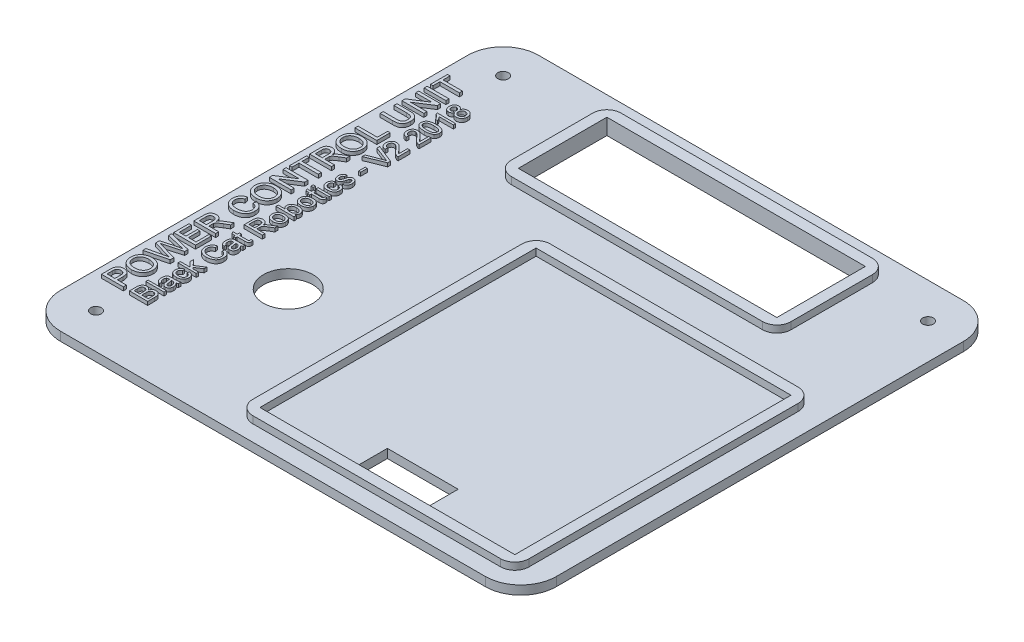
SolidWorks part; units mm, degrees
note: The reader was unsure of these and kept them because the rebuilt part matched: shared geometry of "Sketch1<3>".
ref_plane "Front Plane" through (0, 0, 0) normal (0, 0, 1) x (1, 0, 0)
ref_plane "Top Plane" through (0, 0, 0) normal (0, 1, 0) x (1, 0, 0)
ref_plane "Right Plane" through (0, 0, 0) normal (1, 0, 0) x (0, 0, -1)
sketch "Sketch1" plane through (0, 0, 0) normal (0, 1, 0) x (1, 0, 0)
  line L0 (0, 0) -> (0, -40) construction
  line L1 (0, 0) -> (101.6, 0)
  line L2 (0, 0) -> (0, 48.26)
  line L3 (0, 48.26) -> (101.6, 48.26)
  line L4 (101.6, 0) -> (101.6, 48.26)
  line L5 (0, 48.26) -> (101.6, 48.26)
  line L6 (0, 48.26) -> (0, 81.28)
  line L7 (0, 81.28) -> (101.6, 81.28)
  line L8 (101.6, 48.26) -> (101.6, 81.28)
  line L9 (0, -40) -> (-35, -40) construction
  line L10 (101.6, 81.28) -> (151.6, 81.28) construction
  line L11 (151.5601, 121.6473) -> (151.6, 121.28) construction
  line L12 (151.6, 121.28) -> (151.6, 81.28) construction
  line L18 (-35, -40) -> (151.6, -40)
  line L19 (-35, -40) -> (-35, 121.28)
  line L20 (-35, 121.28) -> (151.6, 121.28)
  line L21 (151.6, -40) -> (151.6, 121.28)
  circle A0 centre (0, 81.28) radius 5
  circle A1 centre (0, 48.26) radius 5
  circle A2 centre (0, 0) radius 5
  circle A3 centre (101.6, 0) radius 5
  circle A4 centre (101.6, 48.26) radius 5
  circle A5 centre (101.6, 81.28) radius 5
  dimension "D5" = 101.6
  dimension "D1" = 40
  dimension "D2" = 35
  dimension "D3" = 50
  dimension "D4" = 40
  dimension "D6" = 48.26
  dimension "D7" = 33.02
extrude "Boss-Extrude1" add sketch "Sketch1" along normal blind 5
extrude "Boss-Extrude2" add sketch "Sketch1<3>" along normal blind 25 contours L7 A0 L6 | A1 | A5 | A4 | A3 | A2
sketch "Sketch1<3>" plane through (0, 0, 0) normal (0, 1, 0) x (1, 0, 0) same geometry as "Sketch1"
fillet "Fillet1" radius 5 6 edges at (101.6, 5, -76.28) (101.6, 5, -43.26) (101.6, 5, 5) (0, 5, 5) (0, 5, -43.26) (0, 5, -76.28)
fillet "Fillet2" radius 20 4 edges at (-35, 2.5, -121.28) (151.6, 2.5, -121.28) (151.6, 2.5, 40) (-35, 2.5, 40)
sketch "Sketch5" plane through (0, 0, 0) normal (0, -1, 0) x (-1, 0, 0)
  line L2 (35, -20) -> (35, 101.28)
  line L4 (-151.6, -20) -> (-151.6, 101.28)
  line L5 (15, -40) -> (-131.6, -40)
  line L7 (15, 121.28) -> (-131.6, 121.28)
  arc A1 (-151.6, -20) -> (-131.6, -40) centre (-131.6, -20) ccw
  arc A2 (-131.6, 121.28) -> (-151.6, 101.28) centre (-131.6, 101.28) ccw
  arc A3 (35, 101.28) -> (15, 121.28) centre (15, 101.28) ccw
  arc A4 (15, -40) -> (35, -20) centre (15, -20) ccw
extrude "Extrude-Thin1" add sketch "Sketch5" against normal blind 80 thin thin type one direction wall 5
hole_wizard "Ø3.0mm Dowel Hole1" positions "3DSketch1" profile "Sketch6" hole size "Ø3.0" standard "ANSI Metric"
sketch3d "3DSketch1"
  line L0 (0, 25, -81.28) -> (0, 10, -81.28) construction
  line L1 (0, 25, -48.26) -> (0, 10, -48.26) construction
  line L2 (0, 25, 0) -> (0, 10, 0) construction
  line L3 (101.6, 25, -81.28) -> (101.6, 10, -81.28) construction
  line L4 (101.6, 25, -48.26) -> (101.6, 10, -48.26) construction
  line L5 (101.6, 25, 0) -> (101.6, 10, 0) construction
  point P0 (0, 25, -81.28)
  point P4 (0, 25, -48.26)
  point P8 (0, 25, 0)
  point P12 (101.6, 25, -81.28)
  point P16 (101.6, 25, -48.26)
  point P20 (101.6, 25, 0)
sketch "Sketch6" plane through (0, 25, -81.28) normal (1, 0, 0) x (0, 0, 1)
  line L0 (0, 0) -> (0, 10.9013)
  line L1 (0, 10.9013) -> (1.5, 10)
  line L2 (1.5, 10) -> (1.5, 0)
  line L5 (1.5, 0) -> (0, 0)
  line L10 (0, 10.9013) -> (-1.5, 10) construction
  line L11 (0, -6.35) -> (0, 107.95) construction
  dimension "Hole Dia." = 3
  dimension "Hole Depth" = 10
  dimension "Drill Angle" = 118
sketch "Sketch7" plane through (0, 5, 0) normal (0, 1, 0) x (1, 0, 0)
  line L0 (-15, 121.28) -> (131.6, 121.28) construction
  line L1 (-15, 121.28) -> (0, 121.28)
  line L2 (-15, 121.28) -> (-15, 109.28)
  line L3 (-15, 109.28) -> (0, 109.28)
  line L4 (0, 121.28) -> (0, 109.28)
  line L5 (131.6, 121.28) -> (111.6, 121.28)
  line L6 (131.6, 121.28) -> (131.6, 109.28)
  line L7 (131.6, 109.28) -> (111.6, 109.28)
  line L8 (111.6, 121.28) -> (111.6, 109.28)
  line L10 (131.6, -40) -> (-15, -40) construction
  line L11 (-15, -40) -> (131.6, -40) construction
  line L12 (60.8, -28) -> (70.8, -28)
  line L14 (58.3, -40) -> (70.8, -40)
  line L15 (70.8, -28) -> (70.8, -40)
  line L16 (60.8, -28) -> (50.8, -28)
  line L18 (58.3, -40) -> (50.8, -40)
  line L19 (50.8, -28) -> (50.8, -40)
  arc A0 (151.6, 101.28) -> (131.6, 121.28) centre (131.6, 101.28) ccw construction
  dimension "D1" = 12
extrude "Boss-Extrude3" add sketch "Sketch7" along normal blind 75
fillet "Fillet3" radius 5 8 edges at (111.6, 42.5, -121.28) (131.6, 42.5, -121.28) (131.6, 42.5, -109.28) (111.6, 42.5, -109.28) (0, 42.5, -121.28) (0, 42.5, -109.28) (-15, 42.5, -109.28) (-15, 42.5, -121.28)
fillet "Fillet4" radius 5 4 edges at (70.8, 42.5, 28) (70.8, 42.5, 40) (50.8, 42.5, 28) (50.8, 42.5, 40)
sketch "Sketch13" plane through (0, 80, 0) normal (0, 1, 0) x (1, 0, 0)
  line L0 (-7.5, 109.28) -> (-7.5, 126.28)
  line L1 (-10, 109.28) -> (-5, 109.28) construction
  line L2 (-15, 126.28) -> (131.6, 126.28) construction
  line L3 (121.6, 109.28) -> (121.6, 126.28)
  line L4 (116.6, 109.28) -> (126.6, 109.28) construction
  line L5 (60.8, -45) -> (60.8, -28)
  line L7 (65.8, -28) -> (55.8, -28) construction
  circle A0 centre (60.8, -36.5) radius 5
  circle A1 centre (-7.5, 117.78) radius 5
  circle A2 centre (121.6, 117.78) radius 5
sketch "Sketch16" plane through (0, 0, 45) normal (0, 0, 1) x (1, 0, 0)
  line L1 (-15, 80) -> (-5, 80)
  line L2 (-15, 80) -> (-15, 30)
  line L3 (-15, 30) -> (-5, 30)
  line L4 (-5, 80) -> (-5, 30)
  line L5 (131.6, 80) -> (116.6, 80)
  line L6 (131.6, 80) -> (131.6, 30)
  line L7 (131.6, 30) -> (116.6, 30)
  line L8 (116.6, 80) -> (116.6, 30)
extrude "Cut-Extrude1" cut sketch "Sketch16" against normal blind 10
fillet "Fillet5" radius 5 4 edges at (-15, 30, 42.5) (-5, 30, 42.5) (131.6, 30, 42.5) (116.6, 30, 42.5)
sketch "Sketch17" plane through (0, 80, 0) normal (0, 1, 0) x (1, 0, 0)
  line L1 (-57.274, 131.034) -> (186.0736, 131.034)
  line L2 (-57.274, 131.034) -> (-57.274, -55.1965)
  line L3 (-57.274, -55.1965) -> (186.0736, -55.1965)
  line L4 (186.0736, 131.034) -> (186.0736, -55.1965)
extrude "Cut-Extrude2" cut sketch "Sketch17" against normal blind 75
sketch "Sketch18" plane through (0, 5, 0) normal (0, 1, 0) x (1, 0, 0)
  line L0 (94.8, 73.78) -> (94.8, -21.22)
  line L1 (-15, 126.28) -> (131.6, 126.28) construction
  line L2 (21.8, 13.78) -> (16.8, 13.78)
  line L3 (69.8, -21.22) -> (89.8, -21.22)
  line L8 (94.8, 73.78) -> (21.8, 73.78)
  line L9 (94.8, 73.78) -> (94.8, 98.78)
  line L10 (94.8, 98.78) -> (21.8, 98.78)
  line L15 (94.8, -21.22) -> (69.8, -21.22)
  line L16 (58.3, 126.28) -> (58.3, 86.28)
  line L17 (21.8, 73.78) -> (21.8, 98.78)
  line L22 (94.8, 73.78) -> (21.8, 98.78) construction
  line L23 (94.8, 98.78) -> (21.8, 73.78) construction
  line L24 (69.8, -21.22) -> (69.8, -11.22)
  line L25 (21.8, 73.78) -> (21.8, 13.78)
  line L26 (69.8, -11.22) -> (89.8, -11.22)
  line L27 (89.8, -21.22) -> (89.8, -11.22)
  circle A2 centre (16.8, 13.78) radius 7
  dimension "D3" = 25
  dimension "D2" = 95
  dimension "D7" = 20
  dimension "D1" = 73
  dimension "D4" = 25
  dimension "D5" = 60
  dimension "D6" = 5
extrude "Cut-Extrude3" cut sketch "Sketch18" against normal blind 10
sketch "Sketch21" plane through (0, 5, 0) normal (0, 1, 0) x (1, 0, 0)
  line L1 (21.8, 98.78) -> (94.8, 98.78)
  line L2 (21.8, 98.78) -> (21.8, 73.78)
  line L3 (21.8, 73.78) -> (94.8, 73.78)
  line L4 (94.8, 98.78) -> (94.8, 73.78)
extrude "Extrude-Thin2" add sketch "Sketch21" along normal blind 2 thin thin type one direction wall 3
sketch "Sketch22" plane through (0, 5, 0) normal (0, 1, 0) x (1, 0, 0)
  line L0 (79.8, -21.22) -> (43.8, -21.22)
  line L2 (69.8, -21.22) -> (89.8, -21.22) construction
  line L8 (43.8, -21.22) -> (115.8, -21.22)
  line L9 (43.8, -21.22) -> (43.8, 56.78)
  line L10 (43.8, 56.78) -> (115.8, 56.78)
  line L11 (115.8, -21.22) -> (115.8, 56.78)
  dimension "D1" = 36
  dimension "D2" = 72
  dimension "D3" = 78
extrude "Extrude-Thin3" add sketch "Sketch22" along normal blind 2 thin contours L8 L11 L10 L9 thin type one direction wall 3
fillet "Fillet6" radius 4 8 edges at (118.8, 6, -59.78) (118.8, 6, 24.22) (40.8, 6, 24.22) (40.8, 6, -59.78) (18.8, 6, -101.78) (97.8, 6, -101.78) (97.8, 6, -70.78) (18.8, 6, -70.78)
sketch "Sketch23" plane through (0, 5, 0) normal (0, 1, 0) x (1, 0, 0)
  line L0 (-15, 126.28) -> (-15, 106.28)
  line L1 (-15, 106.28) -> (125, 106.28)
  line L2 (125, 106.28) -> (125, -28.72)
  line L3 (125, -28.72) -> (-15, -28.72)
  line L4 (-15, -28.72) -> (-15, 106.28)
  line L6 (-53.8165, 126.28) -> (168.4095, 126.28)
  line L7 (-53.8165, 126.28) -> (-53.8165, -53.2805)
  line L8 (-53.8165, -53.2805) -> (168.4095, -53.2805)
  line L9 (168.4095, 126.28) -> (168.4095, -53.2805)
extrude "Cut-Extrude4" cut sketch "Sketch23" against normal blind 10
sketch "Sketch24" plane through (0, 0, 0) normal (0, -1, 0) x (1, 0, 0)
  line L1 (-25.72, 37.3701) -> (138.6787, 37.3701)
  line L2 (-25.72, 37.3701) -> (-25.72, -115.4799)
  line L3 (-25.72, -115.4799) -> (138.6787, -115.4799)
  line L4 (138.6787, 37.3701) -> (138.6787, -115.4799)
extrude "Cut-Extrude5" cut sketch "Sketch24" against normal blind 2.5
fillet "Fillet7" radius 10 4 edges at (-15, 3.75, -106.28) (125, 3.75, -106.28) (125, 3.75, 28.72) (-15, 3.75, 28.72)
sketch "Sketch25" plane through (0, 5, 0) normal (0, 1, 0) x (1, 0, 0)
  circle A0 centre (-5, 96.28) radius 5
  circle A1 centre (115, 96.28) radius 5
  circle A2 centre (-5, -18.72) radius 5
hole_wizard "Ø3.0mm Dowel Hole2" positions "3DSketch2" profile "Sketch26" hole size "Ø3.0" standard "ANSI Metric" end condition through all
sketch3d "3DSketch2"
  point P0 (-5, 5, 18.72)
  point P3 (-5, 5, -96.28)
  point P6 (115, 5, -96.28)
sketch "Sketch26" plane through (-5, 5, 18.72) normal (1, 0, 0) x (0, 0, 1)
  line L0 (0, 0) -> (0, 2.5)
  line L1 (0, 2.5) -> (1.5, 2.5)
  line L2 (1.5, 2.5) -> (1.5, 0)
  line L5 (1.5, 0) -> (0, 0)
  line L11 (0, -6.35) -> (0, 107.95) construction
  dimension "Thru Hole Dia." = 3
  dimension "Thru Hole Depth" = 2.5
sketch "Sketch27" plane through (0, 5, 0) normal (0, 1, 0) x (1, 0, 0)
  line L0 (-6, -10.72) -> (1, -10.72) construction
  line L1 (-15, -18.72) -> (-15, -10.72) construction
  line L2 (-15, -18.72) -> (-15, 96.28) construction
  line L3 (-15, -10.72) -> (-6, -10.72) construction
  line L4 (-6, -10.72) -> (-6, 106.28) construction
  line L5 (-5, 106.28) -> (115, 106.28) construction
  line L6 (1, -10.72) -> (1, 106.28) construction
  text T0 "POWER CONTROL UNIT" font "Arial" height in points 24
  text T1 "Black Cat Robotics - V2 2018" font "Arial" height in points 20
  dimension "D1" = 9
  dimension "D2" = 8
  dimension "D3" = 7
extrude "Boss-Extrude4" add sketch "Sketch27" along normal blind 1
